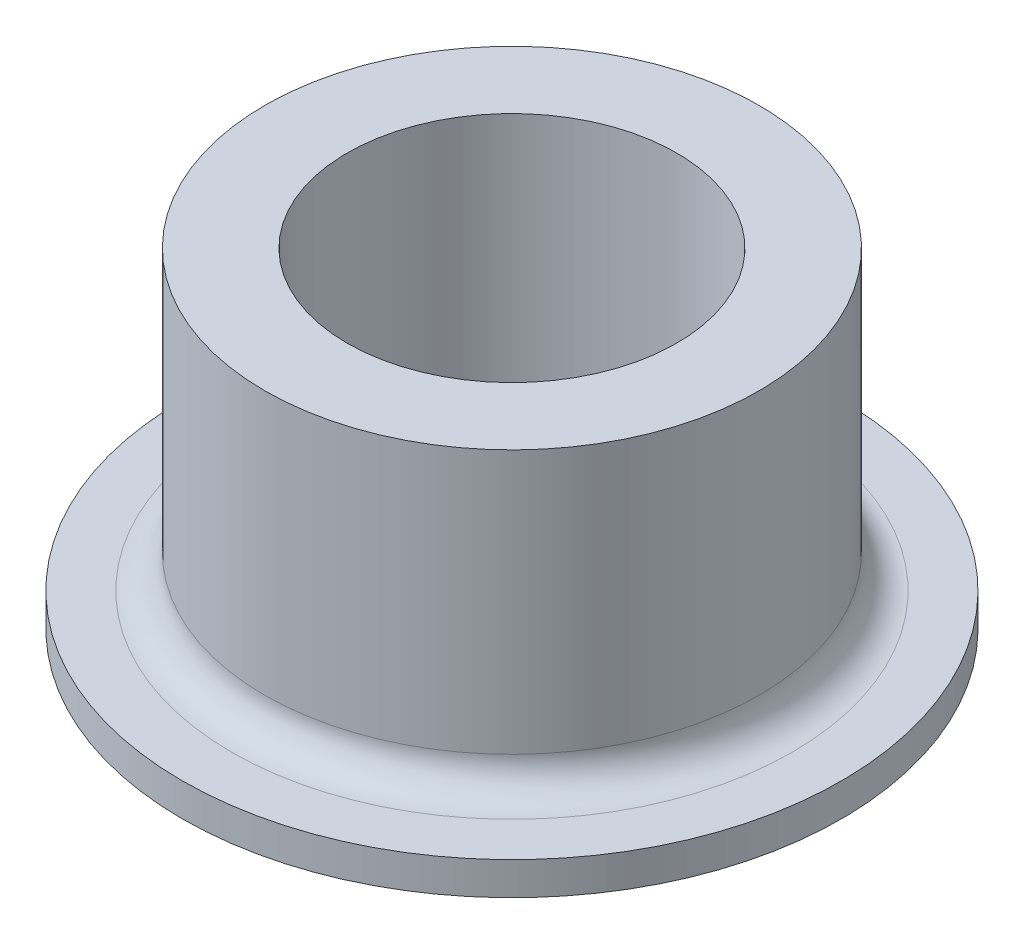
SolidWorks part; units mm, degrees
material "SAE 660 bearing bronze"
ref_plane "Front Plane" through (0, 0, 0) normal (1, 0, 0) x (0, 1, 0)
ref_plane "Top Plane" through (0, 0, 0) normal (0, 0, 1) x (0, 1, 0)
ref_plane "Right Plane" through (0, 0, 0) normal (0, 1, 0) x (-1, 0, 0)
sketch "Sketch1" plane through (0, 0, 0) normal (0, 1, 0) x (-1, 0, 0)
  circle A0 centre (0, 0) radius 10
  circle A1 centre (0, 0) radius 7.5
  circle A2 centre (0, 0) radius 5
  dimension "D1" = 20
  dimension "D2" = 15
  dimension "D3" = 10
extrude "Boss-Extrude1" add sketch "Sketch1" along normal blind 1 contours A0 A1 region at (9.7172, 0, 0)
extrude "Boss-Extrude2" add sketch "Sketch1<3>" along normal blind 10 contours A1 A2 region at (7.2879, 0, 0)
sketch "Sketch1<3>" plane through (0, 0, 0) normal (0, 1, 0) x (-1, 0, 0) same geometry as "Sketch1"
ref_axis "Axis1" through (0, 11.0668, 0) along (0, 1, 0)
fillet "Fillet1" radius 1 1 edges at (0, 1, 7.5)
